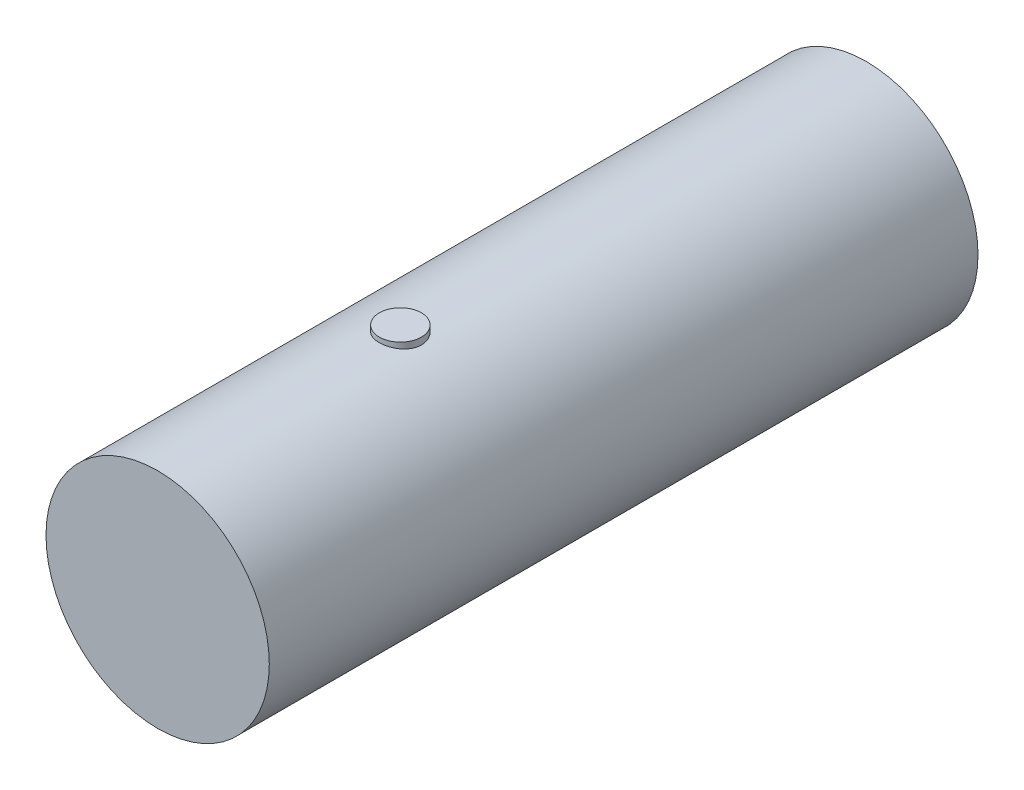
SolidWorks part; units mm, degrees
ref_plane "Ebene vorne" through (0, 0, 0) normal (0, 0, 1) x (1, 0, 0)
ref_plane "Ebene oben" through (0, 0, 0) normal (0, 1, 0) x (1, 0, 0)
ref_plane "Ebene rechts" through (0, 0, 0) normal (1, 0, 0) x (0, 0, -1)
sketch "Skizze1" plane through (0, 0, 0) normal (0, 0, 1) x (1, 0, 0)
  circle A0 centre (0, 0) radius 115
  dimension "D1" = 230
extrude "Aufsatz-Linear austragen1" add sketch "Skizze1" along normal blind 730
sketch "Skizze2" plane through (0, 0, 0) normal (0, 1, 0) x (1, 0, 0)
  line L0 (0, -730) -> (0, 0) construction
  line L1 (-115, -730) -> (115, -730) construction
  circle A0 centre (0, -480) radius 21.6863
  dimension "D1" = 250
extrude "Aufsatz-Linear austragen2" add sketch "Skizze2" along normal blind 120 and the other way blind 120
